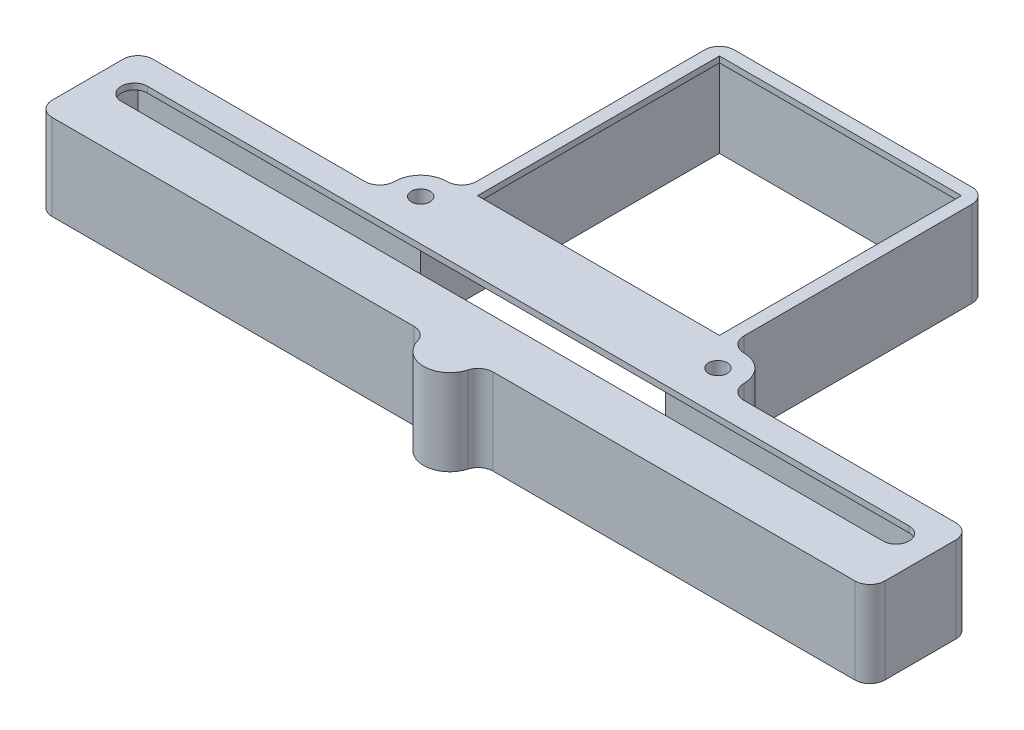
SolidWorks part; units mm, degrees
ref_plane "Front Plane" through (0, 0, 0) normal (0, 0, 1) x (1, 0, 0)
ref_plane "Top Plane" through (0, 0, 0) normal (0, 1, 0) x (1, 0, 0)
ref_plane "Right Plane" through (0, 0, 0) normal (1, 0, 0) x (0, 0, -1)
sketch "Sketch1" plane through (0, 0, 0) normal (0, 1, 0) x (1, 0, 0)
  line L0 (0, 36.3641) -> (0, -33.052) construction
  line L1 (-16.4, 25.25) -> (16.4, 25.25)
  line L2 (-16.4, 25.25) -> (-16.4, -25.25)
  line L3 (-16.4, -25.25) -> (16.4, -25.25)
  line L4 (16.4, 25.25) -> (16.4, -25.25)
  line L5 (-16.4, 25.25) -> (16.4, -25.25) construction
  line L6 (-16.4, -25.25) -> (16.4, 25.25) construction
  line L7 (-16.4, -25.25) -> (-16.4, -26.75) construction
  line L12 (-54.25, -14.75) -> (-55.75, -14.75) construction
  line L13 (-54.25, -14.75) -> (54.25, -14.75)
  line L14 (17.9, -26.75) -> (-17.9, -26.75)
  line L15 (17.9, -26.75) -> (17.9, 26.75)
  line L16 (17.9, 26.75) -> (-17.9, 26.75)
  line L17 (-17.9, -26.75) -> (-17.9, 26.75)
  line L18 (17.9, -26.75) -> (-17.9, 26.75) construction
  line L19 (17.9, 26.75) -> (-17.9, -26.75) construction
  line L20 (-16.4, 25.25) -> (-17.9, 25.25) construction
  line L21 (-16.4, 25.25) -> (-16.4, 26.75) construction
  line L22 (-54.25, -14.75) -> (-54.25, -25.25)
  line L23 (-54.25, -25.25) -> (54.25, -25.25)
  line L24 (54.25, -14.75) -> (54.25, -25.25)
  line L25 (-54.25, -14.75) -> (54.25, -25.25) construction
  line L26 (-54.25, -25.25) -> (54.25, -14.75) construction
  line L27 (-55.75, -13.25) -> (55.75, -13.25)
  line L28 (-55.75, -13.25) -> (-55.75, -26.75)
  line L29 (-55.75, -26.75) -> (55.75, -26.75)
  line L30 (55.75, -13.25) -> (55.75, -26.75)
  line L31 (-55.75, -13.25) -> (55.75, -26.75) construction
  line L32 (-55.75, -26.75) -> (55.75, -13.25) construction
  line L33 (-2, -27.25) -> (-3.5, -27.25) construction
  line L34 (-3.5, -27.25) -> (-3.5, -26.75)
  line L35 (3.5, -27.25) -> (3.5, -26.75)
  line L36 (-2, -27.25) -> (-2, -25.25)
  line L37 (2, -27.25) -> (2, -25.25)
  circle A0 centre (0, -27.25) radius 2
  circle A1 centre (0, -27.25) radius 3.5
  point P0 (0, 0)
  point P7 (0, -20)
  point P11 (0, -20)
  point P13 (0, 0)
  dimension "D6" = 4
  dimension "D1" = 32.8
  dimension "D2" = 50.5
  dimension "D3" = 1.5
  dimension "D4" = 108.5
  dimension "D5" = 10.5
extrude "Boss-Extrude1" add sketch "Sketch1" along normal blind 11.5 contours L17 L16 L15 L14 | L27 L30 L29 L28 | A1
sketch "Sketch2" plane through (0, 11.5, 0) normal (0, 1, 0) x (1, 0, 0)
  line L0 (0, 26.75) -> (0, -30.75) construction
  line L1 (17.9, 26.75) -> (-17.9, 26.75) construction
  line L3 (-16.2, 25.05) -> (-17.9, 25.05) construction
  line L4 (-16.2, -7.35) -> (16.2, -7.35)
  line L5 (-16.2, -7.35) -> (-16.2, 25.05)
  line L6 (-16.2, 25.05) -> (16.2, 25.05)
  line L7 (16.2, -7.35) -> (16.2, 25.05)
  line L8 (-16.2, -7.35) -> (16.2, 25.05) construction
  line L9 (-16.2, 25.05) -> (16.2, -7.35) construction
  line L10 (-17.9, -13.25) -> (-17.9, 26.75) construction
  line L11 (-16.2, 25.05) -> (-16.2, 26.75) construction
  arc A0 (-3.4641, -26.75) -> (3.4641, -26.75) centre (0, -27.25) ccw construction
  point P6 (0, 8.85)
  dimension "D1" = 32.4
extrude "Cut-Extrude1" cut sketch "Sketch2" against normal blind 8.7
sketch "Sketch3" plane through (0, 0, 0) normal (0, -1, 0) x (1, 0, 0)
  line L0 (-55.75, 20) -> (55.75, 20) construction
  line L1 (-55.75, 13.25) -> (-55.75, 26.75) construction
  line L2 (55.75, 13.25) -> (55.75, 26.75) construction
  line L3 (0, 30.75) -> (0, -26.75) construction
  line L4 (55.75, 26.75) -> (3.4641, 26.75) construction
  line L5 (17.9, -26.75) -> (-17.9, -26.75) construction
  line L6 (-54.25, 25.25) -> (-55.75, 25.25) construction
  line L7 (-54.25, 25.25) -> (54.25, 25.25)
  line L8 (-54.25, 25.25) -> (-54.25, 14.75)
  line L9 (-54.25, 14.75) -> (54.25, 14.75)
  line L10 (54.25, 25.25) -> (54.25, 14.75)
  line L11 (-54.25, 25.25) -> (54.25, 14.75) construction
  line L12 (-54.25, 14.75) -> (54.25, 25.25) construction
  line L13 (-54.25, 25.25) -> (-54.25, 26.75) construction
  line L14 (-2, 27.25) -> (-2, 25.25)
  line L15 (2, 27.25) -> (2, 25.25)
  arc A0 (3.4641, 26.75) -> (-3.4641, 26.75) centre (0, 27.25) ccw construction
  circle A1 centre (0, 27.25) radius 2
  point P12 (0, 20)
  dimension "D2" = 4
  dimension "D1" = 1.5
extrude "Cut-Extrude2" cut sketch "Sketch3" against normal offset from surface (10.7 mm away) 0.8 contours A1 | A1 L14 L7 | A1 L7 L15 | L10 L7 L8 L9 region at (0, 0, 20) region at (-1.5533, 0, 25.6967) region at (1.5533, 0, 25.6967) region at (0, 0, 27.25) up to face at (0, 11.5, -8.85)
sketch "Sketch4" plane through (0, 10.7, 0) normal (0, -1, 0) x (1, 0, 0)
  line L0 (-54.25, 18.5) -> (54.25, 18.5) construction
  line L1 (-54.25, 14.75) -> (-54.25, 25.25) construction
  line L2 (54.25, 25.25) -> (54.25, 14.75) construction
  line L3 (54.25, 14.75) -> (-54.25, 14.75) construction
  line L4 (51, 18.5) -> (-51, 18.5) construction
  line L5 (51, 16.75) -> (-51, 16.75)
  line L6 (51, 20.25) -> (-51, 20.25)
  arc A0 (51, 16.75) -> (51, 20.25) centre (51, 18.5) ccw
  arc A1 (-51, 20.25) -> (-51, 16.75) centre (-51, 18.5) ccw
  point P10 (0, 18.5)
  dimension "D1" = 3.75
  dimension "D2" = 3.5
  dimension "D3" = 102
extrude "Cut-Extrude3" cut sketch "Sketch4" against normal up to next
sketch "Sketch5" plane through (0, 0, 0) normal (0, -1, 0) x (1, 0, 0)
  line L0 (-17.9, -6.75) -> (17.9, -6.75) construction
  line L1 (-17.9, 13.25) -> (-17.9, -26.75) construction
  line L2 (17.9, 13.25) -> (17.9, -26.75) construction
  line L3 (-17.9, 13.25) -> (17.9, 13.25) construction
  line L4 (0, -26.75) -> (0, 13.25) construction
  line L5 (17.9, -26.75) -> (-17.9, -26.75) construction
  line L7 (-16.4, 14.75) -> (16.4, 14.75)
  line L8 (-16.4, 14.75) -> (-16.4, -25.25)
  line L9 (-16.4, -25.25) -> (16.4, -25.25)
  line L10 (16.4, 14.75) -> (16.4, -25.25)
  line L11 (-16.4, 14.75) -> (16.4, -25.25) construction
  line L12 (-16.4, -25.25) -> (16.4, 14.75) construction
  line L13 (54.25, 14.75) -> (-54.25, 14.75) construction
  line L14 (16.4, -25.25) -> (17.9, -25.25) construction
  line L15 (16.4, -25.25) -> (16.4, -26.75) construction
  point P14 (0, -5.25)
  dimension "D1" = 1.5
extrude "Cut-Extrude4" cut sketch "Sketch5" against normal up to surface (10.7 mm away) up to face at (0, 10.7, 18.5)
sketch "Sketch6" plane through (0, 10.7, 0) normal (0, -1, 0) x (1, 0, 0)
  line L0 (-16.4, -25.25) -> (-16.4, 14.75) construction
  line L1 (-16.4, 7.35) -> (16.4, 7.35)
  line L2 (-16.4, 7.35) -> (-16.4, 8.85)
  line L3 (-16.4, 8.85) -> (16.4, 8.85)
  line L4 (16.4, 7.35) -> (16.4, 8.85)
  line L5 (16.4, -25.25) -> (16.4, 14.75) construction
  line L7 (-16.2, 7.35) -> (16.2, 7.35) construction
  dimension "D1" = 1.5
extrude "Boss-Extrude2" add sketch "Sketch6" along normal offset from surface (7.7 mm away) 8.5 up to face at (0, 11.5, 18.5)
sketch "Sketch8" plane through (0, 11.5, 0) normal (0, 1, 0) x (1, 0, 0)
  line L0 (-55.75, -13.25) -> (-17.9, -13.25) construction
  line L2 (0, 31.5428) -> (0, -38.2394) construction
  line L3 (-19.9, -7.75) -> (-17.9, -7.75)
  line L4 (-17.9, -13.25) -> (-17.9, 26.75) construction
  line L5 (-23.4, -11.25) -> (-23.4, -13.25)
  line L6 (23.4, -11.25) -> (23.4, -13.25)
  line L7 (19.9, -7.75) -> (17.9, -7.75)
  line L8 (-23.4, -13.25) -> (-17.9, -13.25)
  line L9 (-17.9, -13.25) -> (-17.9, -7.75)
  line L10 (17.9, -13.25) -> (17.9, -7.75)
  line L11 (23.4, -13.25) -> (17.9, -13.25)
  circle A0 centre (-19.9, -11.25) radius 2
  circle A1 centre (19.9, -11.25) radius 2
  circle A2 centre (-19.9, -11.25) radius 3.5
  circle A3 centre (19.9, -11.25) radius 3.5
  circle A4 centre (-19.9, -11.25) radius 1.25
  circle A5 centre (19.9, -11.25) radius 1.25
  line M16 (-17.9, 26.75) -> (-17.9, -13.25)
  line M17 (-17.9, -13.25) -> (-55.75, -13.25)
  line M21 (55.75, -13.25) -> (17.9, -13.25)
  line M22 (17.9, -13.25) -> (17.9, 26.75)
  dimension "D1" = 4
  dimension "D3" = 1.5
  dimension "D2" = 2.5
extrude "Boss-Extrude5" add sketch "Sketch8" against normal up to surface (11.5 mm away) contours A2 L3 M16 | L9 A2 L8 A0 | A0 A4 | A0 L9 M17 | A2 L5 M17 | L11 A1 M22 | A1 A5 | A3 L10 A1 L11 | A3 L7 M22 | L6 A3 M21 region at (-18.8752, 11.5, 7.9848) region at (-18.3906, 11.5, 7.935) region at (-23.215, 11.5, 12.7594) region at (-18.5258, 11.5, 12.6242) region at (-18.3467, 11.5, 12.8033) region at (23.1652, 11.5, 12.2748) region at (23.215, 11.5, 12.7594) region at (18.3906, 11.5, 7.935) region at (18.3467, 11.5, 12.8033) region at (18.5258, 11.5, 12.6242) up to face at (0, 0, 13.8333)
fillet "Fillet1" radius 2 12 edges at (55.75, 5.75, 26.75) (55.75, 5.75, 13.25) (-55.75, 5.75, 26.75) (-55.75, 5.75, 13.25) (-17.9, 5.75, -26.75) (17.9, 5.75, -26.75) (-17.9, 5.75, 7.75) (-23.4, 5.75, 13.25) (23.4, 5.75, 13.25) (17.9, 5.75, 7.75) (-3.4641, 5.75, 26.75) (3.4641, 5.75, 26.75)
